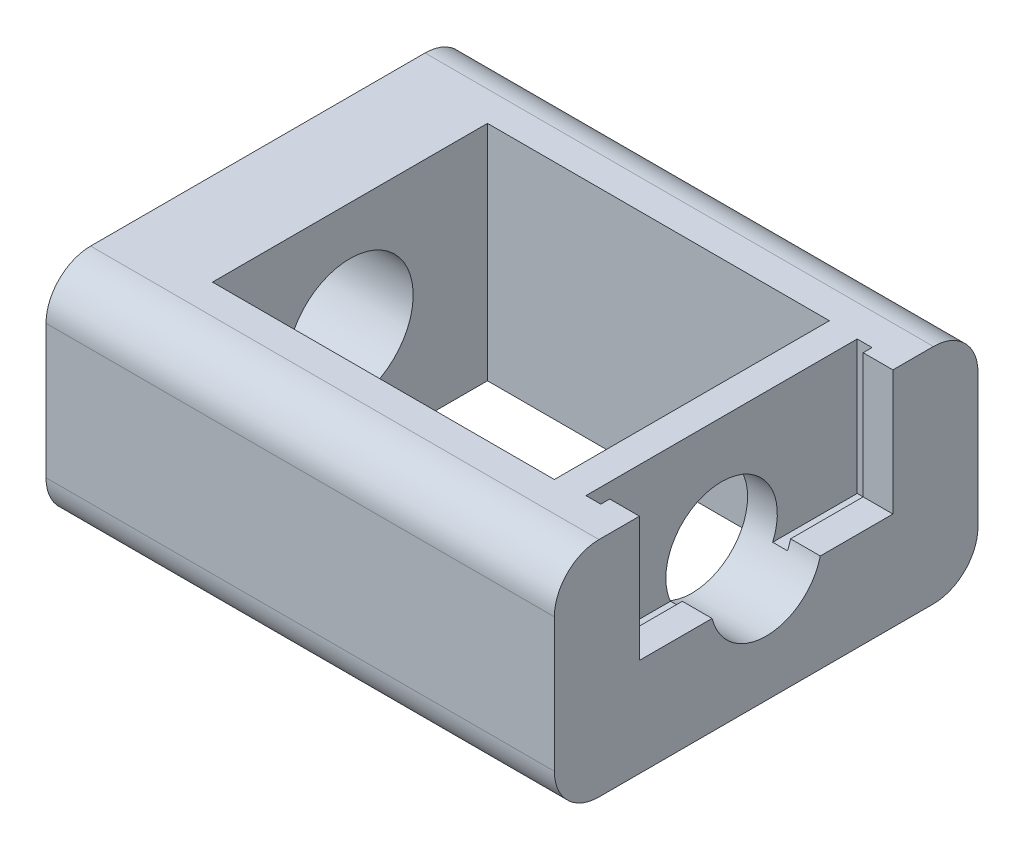
SolidWorks part; units mm, degrees
ref_plane "Front Plane" through (0, 0, 0) normal (0, 0, 1) x (1, 0, 0)
ref_plane "Top Plane" through (0, 0, 0) normal (0, 1, 0) x (1, 0, 0)
ref_plane "Right Plane" through (0, 0, 0) normal (1, 0, 0) x (0, 0, -1)
sketch "Sketch1" plane through (0, 0, 0) normal (1, 0, 0) x (0, 0, -1)
  line L1 (-14.25, -7.5) -> (14.25, -7.5)
  line L2 (-14.25, -7.5) -> (-14.25, 7.5)
  line L3 (-14.25, 7.5) -> (14.25, 7.5)
  line L4 (14.25, -7.5) -> (14.25, 7.5)
  line L5 (-14.25, -7.5) -> (14.25, 7.5) construction
  line L6 (-14.25, 7.5) -> (14.25, -7.5) construction
  circle A0 centre (0, 0) radius 4.25
  point P0 (0, 0)
  dimension "D3" = 8.5
  dimension "D1" = 28.5
  dimension "D2" = 15
extrude "Boss-Extrude1" add sketch "Sketch1" along normal blind 6.2
sketch "Sketch2" plane through (6.2, 0, 0) normal (1, 0, 0) x (0, 0, -1)
  line L0 (14.25, 7.5) -> (-14.25, 7.5) construction
  line L1 (-14.25, 7.5) -> (-9.25, 7.5)
  line L2 (-14.25, 7.5) -> (-14.25, -7.5)
  line L3 (-14.25, -7.5) -> (-9.25, -7.5)
  line L4 (-9.25, 7.5) -> (-9.25, -7.5)
  line L5 (-14.25, 7.5) -> (-9.25, -7.5) construction
  line L6 (-14.25, -7.5) -> (-9.25, 7.5) construction
  line L7 (-14.25, -7.5) -> (14.25, -7.5) construction
  line L8 (0, 0) -> (0, 50000) construction
  line L9 (14.25, -7.5) -> (9.25, -7.5)
  line L10 (9.25, 7.5) -> (9.25, -7.5)
  line L11 (14.25, 7.5) -> (9.25, 7.5)
  line L12 (14.25, 7.5) -> (14.25, -7.5)
  line L13 (-14.25, 7.5) -> (-14.25, -7.5) construction
  point P4 (-11.75, 0)
  point P12 (0, 7.5)
  dimension "D1" = 5
extrude "Boss-Extrude2" add sketch "Sketch2" along normal blind 23
sketch "Sketch3" plane through (29.2, 0, 0) normal (1, 0, 0) x (0, 0, -1)
  line L0 (0, 0) -> (0, 50000) construction
  line L1 (14.25, -7.5) -> (-14.25, -7.5)
  line L2 (14.25, -7.5) -> (14.25, 7.5)
  line L3 (14.25, 7.5) -> (-14.25, 7.5)
  line L4 (-14.25, -7.5) -> (-14.25, 7.5)
  line L5 (14.25, -7.5) -> (-14.25, 7.5) construction
  line L6 (14.25, 7.5) -> (-14.25, -7.5) construction
  line L7 (-8.525, 7.5) -> (-8.525, -0.9)
  line L8 (-9.125, -1.5) -> (9.125, -1.5)
  line L9 (-9.125, -1.5) -> (-9.125, 7.5)
  line L10 (-9.125, 7.5) -> (9.125, 7.5)
  line L11 (9.125, -1.5) -> (9.125, 7.5)
  line L12 (-9.125, -1.5) -> (9.125, 7.5) construction
  line L13 (-9.125, 7.5) -> (9.125, -1.5) construction
  line L14 (-8.525, -0.9) -> (8.525, -0.9)
  line L15 (8.525, -0.9) -> (8.525, 7.5)
  circle A0 centre (0, 0) radius 3.75
  point P4 (0, 0)
  point P9 (0, 3)
  line M9 (-14.25, 7.5) -> (-14.25, -7.5)
  line M10 (-14.25, -7.5) -> (-9.25, -7.5)
  line M11 (-9.25, -7.5) -> (-9.25, 7.5)
  line M12 (-9.25, 7.5) -> (-14.25, 7.5)
  dimension "D6" = 7.5
  dimension "D1" = 9
  dimension "D2" = 18.25
  dimension "D3" = 0.6
  dimension "D4" = 0.6
  dimension "D5" = 0.6
extrude "Boss-Extrude3" add sketch "Sketch3" along normal blind 5 contours M12 M9 M10 M11 | A0 L14 L15 L10 L7 | A0 L8 L9 L3 L1 L2 L11 M11 | A0 L14 L7 L3 L9 L8 | A0 L8 L11 L3 L15 L14 region at (29.2, -2.6295, -4.9759) region at (29.2, 0, 11.75) region at (29.2, 3, -9.0185) region at (29.2, 7.3935, 8.825) region at (29.2, 3.8487, 0)
extrude "Cut-Extrude2" cut sketch "Sketch3<6>" along normal blind 1 from offset 2 contours A0 L14 L15 L10 L7 | A0 L14 L7 L3 L9 L8 | A0 L8 L11 L3 L15 L14 region at (29.2, 3, -9.0185) region at (29.2, 7.3935, 8.825) region at (29.2, 3.8487, 0)
sketch "Sketch3<6>" plane through (29.2, 0, 0) normal (1, 0, 0) x (0, 0, -1) same geometry as "Sketch3"
extrude "Cut-Extrude3" cut sketch "Sketch3<7>" along normal through all from surface contours A0 L14 L15 L10 L7 region at (29.2, 3.8487, 0) starting at face at (31.2, 2.375, 0)
sketch "Sketch3<7>" plane through (29.2, 0, 0) normal (1, 0, 0) x (0, 0, -1) same geometry as "Sketch3"
fillet "Fillet1" radius 3 4 edges at (17.1, 7.5, 14.25) (17.1, -7.5, 14.25) (17.1, 7.5, -14.25) (17.1, -7.5, -14.25)
